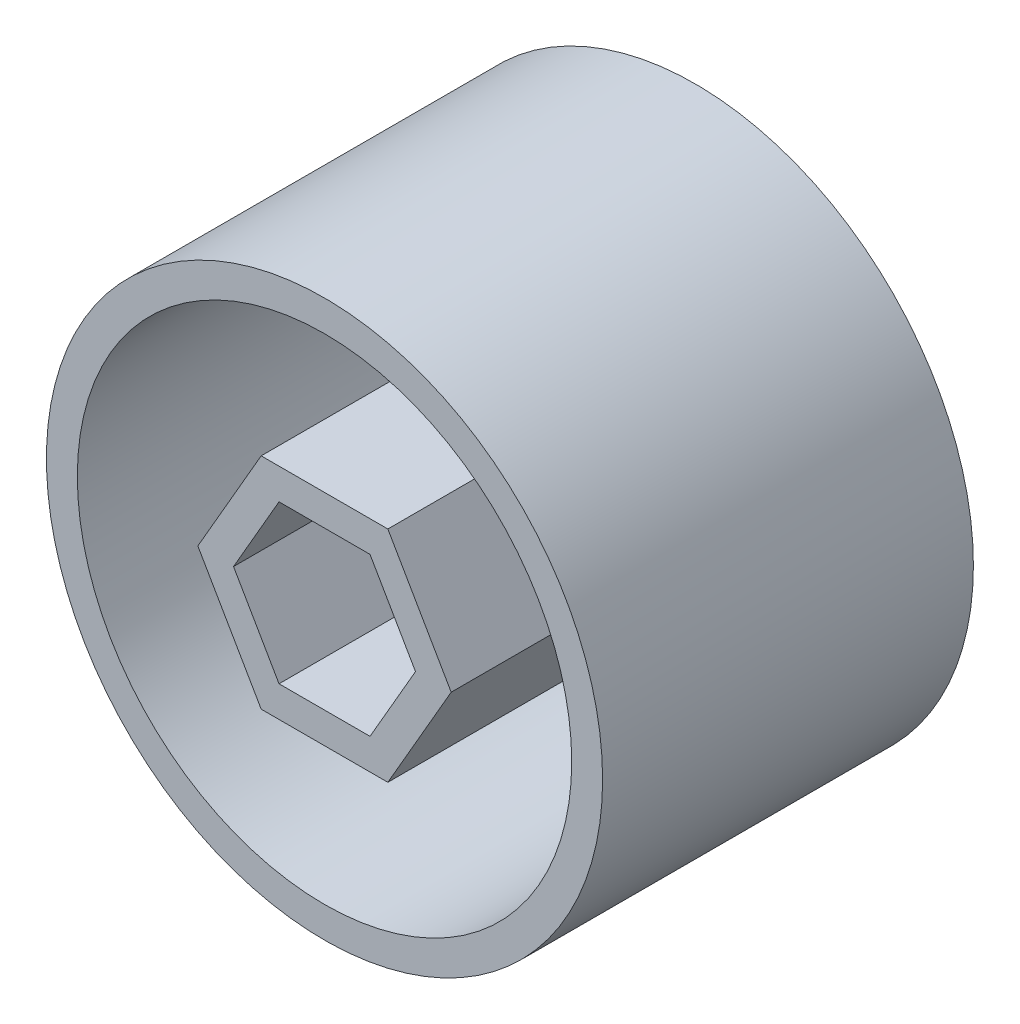
SolidWorks part; units mm, degrees
ref_plane "前视基准面" through (0, 0, 0) normal (0, 0, 1) x (1, 0, 0)
ref_plane "上视基准面" through (0, 0, 0) normal (0, 1, 0) x (1, 0, 0)
ref_plane "右视基准面" through (0, 0, 0) normal (1, 0, 0) x (0, 0, -1)
sketch "草图1" plane through (0, 0, 0) normal (0, 0, 1) x (1, 0, 0)
  line L0 (4.0992, 7.1) -> (-4.0992, 7.1)
  line L1 (5.889, 0) -> (2.9445, 5.1)
  line L2 (2.9445, 5.1) -> (-2.9445, 5.1)
  line L3 (-2.9445, 5.1) -> (-5.889, 0)
  line L4 (-5.889, 0) -> (-2.9445, -5.1)
  line L5 (-2.9445, -5.1) -> (2.9445, -5.1)
  line L6 (2.9445, -5.1) -> (5.889, 0)
  line L7 (-4.0992, 7.1) -> (-8.1984, 0)
  line L8 (-8.1984, 0) -> (-4.0992, -7.1)
  line L9 (-4.0992, -7.1) -> (4.0992, -7.1)
  line L10 (4.0992, -7.1) -> (8.1984, 0)
  line L11 (8.1984, 0) -> (4.0992, 7.1)
  circle A0 centre (0, 0) radius 18
  circle A1 centre (0, 0) radius 16
  circle A2 centre (0, 0) radius 5.1 construction
  dimension "D1" = 36
  dimension "D3" = 10.2
  dimension "D2" = 2
  dimension "D4" = 2
extrude "凸台-拉伸1" add sketch "草图1" along normal blind 24 contours A0 A1 | L10 L11 L0 L7 L8 L9 L6 L5 L4 L3 L2 L1 region at (5.9609, 3.4415, 0) region at (-17.4909, 0, 0)
sketch "草图2" plane through (0, 0, 0) normal (0, 0, -1) x (-1, 0, 0)
  line L0 (2.9445, 5.1) -> (5.889, 0) construction
  line L1 (5.889, 0) -> (2.9445, -5.1) construction
  line L2 (2.9445, -5.1) -> (-2.9445, -5.1) construction
  line L3 (-2.9445, -5.1) -> (-5.889, 0) construction
  line L4 (-5.889, 0) -> (-2.9445, 5.1) construction
  line L5 (-2.9445, 5.1) -> (2.9445, 5.1) construction
  line L6 (2.9445, 5.1) -> (5.889, 0)
  line L7 (5.889, 0) -> (2.9445, -5.1)
  line L8 (2.9445, -5.1) -> (-2.9445, -5.1)
  line L9 (-2.9445, -5.1) -> (-5.889, 0)
  line L10 (-5.889, 0) -> (-2.9445, 5.1)
  line L11 (-2.9445, 5.1) -> (2.9445, 5.1)
  circle A0 centre (0, 0) radius 18
  circle A1 centre (0, 0) radius 18 construction
extrude "凸台-拉伸2" add sketch "草图2" against normal blind 2
ref_plane "基准面1" through (0, 0, 12) normal (0, 0, -1) x (-1, 0, 0)
